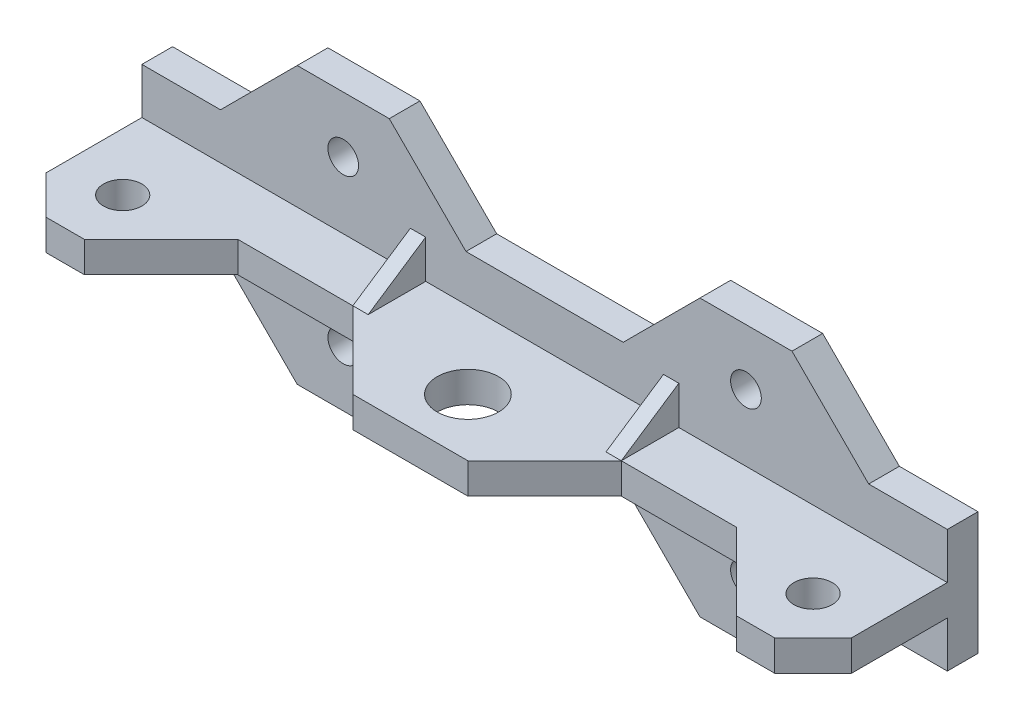
SolidWorks part; units mm, degrees
ref_plane "Front Plane" through (0, 0, 0) normal (0, 0, 1) x (1, 0, 0)
ref_plane "Top Plane" through (0, 0, 0) normal (0, 1, 0) x (1, 0, 0)
ref_plane "Right Plane" through (0, 0, 0) normal (1, 0, 0) x (0, 0, -1)
sketch "Sketch2" plane through (0, 0, 0) normal (0, 1, 0) x (1, 0, 0)
  line L2 (-52.5, 10) -> (52.5, 10)
  line L27 (-45, 0) -> (45, 0) construction
  line L34 (-50.1202, 2.5) -> (-6.1027, 2.5) construction
  line L36 (0, 10) -> (0, -7.5) construction
  line L37 (7.5, -7.5) -> (-7.5, -7.5)
  line L40 (-32.5, 2.5) -> (-17.5, 2.5)
  line L41 (-17.5, 2.5) -> (-7.5, -7.5)
  line L42 (50.1202, 2.5) -> (6.1027, 2.5) construction
  line L48 (-52.5, 10) -> (-52.5, 0)
  line L50 (-52.5, -2.5) -> (-47.5, -7.5)
  line L52 (-52.5, 0) -> (-52.5, -2.5)
  line L53 (-47.5, -7.5) -> (-42.5, -7.5)
  line L55 (-42.5, -7.5) -> (-32.5, 2.5)
  line L56 (42.5, -7.5) -> (32.5, 2.5)
  line L57 (47.5, -7.5) -> (42.5, -7.5)
  line L58 (52.5, 0) -> (52.5, -2.5)
  line L59 (52.5, -2.5) -> (47.5, -7.5)
  line L60 (52.5, 10) -> (52.5, 0)
  line L61 (17.5, 2.5) -> (7.5, -7.5)
  line L62 (32.5, 2.5) -> (17.5, 2.5)
  circle A0 centre (0, 0) radius 4
  circle A1 centre (-45, 0) radius 2.5
  circle A3 centre (45, 0) radius 2.5
  point P8 (-52.5, -7.5)
  point P9 (-52.5, -7.5)
  point P11 (-31.7458, 2.5)
  point P18 (0, 0)
  point P23 (0, -10)
  point P34 (52.5, -7.5)
  dimension "D1" = 8
  dimension "D2" = 5
  dimension "D3" = 10
  dimension "D4" = 45
  dimension "D5" = 5
  dimension "D6" = 7.5
  dimension "D7" = 45
  dimension "D8" = 7.5
  dimension "D9" = 45
  dimension "D10" = 17.5
  dimension "D11" = 7.5
  dimension "D12" = 0
  dimension "D14" = 7.5
extrude "Boss-Extrude1" add sketch "Sketch2" along normal blind 2 and the other way blind 2
sketch "Sketch4" plane through (0, 0, -10) normal (0, 0, -1) x (-1, 0, 0)
  line L1 (52.5, -18) -> (-52.5, -18) construction
  line L3 (52.5, 18) -> (-52.5, 18) construction
  line L6 (52.5, -8) -> (42.25, -8)
  line L7 (42.25, -8) -> (32.25, -18)
  line L8 (20.25, -18) -> (10.25, -8)
  line L9 (10.25, -8) -> (-10.25, -8)
  line L10 (52.5, 0) -> (-52.5, 0) construction
  line L11 (0, -18) -> (0, 0) construction
  line L12 (32.25, -18) -> (20.25, -18)
  line L13 (0, -3.3494) -> (52.5, -3.3494) construction
  line L14 (26.25, -3.3494) -> (26.25, -18) construction
  line L15 (52.5, -8) -> (52.5, 8)
  line L16 (-20.25, -18) -> (-10.25, -8)
  line L17 (-32.25, -18) -> (-20.25, -18)
  line L18 (-42.25, -8) -> (-32.25, -18)
  line L19 (-52.5, -8) -> (-42.25, -8)
  line L20 (-52.5, -8) -> (-52.5, 8)
  line L21 (-52.5, 8) -> (-42.25, 8)
  line L22 (-42.25, 8) -> (-32.25, 18)
  line L23 (-32.25, 18) -> (-20.25, 18)
  line L24 (-20.25, 18) -> (-10.25, 8)
  line L25 (10.25, 8) -> (-10.25, 8)
  line L26 (20.25, 18) -> (10.25, 8)
  line L27 (32.25, 18) -> (20.25, 18)
  line L28 (42.25, 8) -> (32.25, 18)
  line L29 (52.5, 8) -> (42.25, 8)
  circle A0 centre (26.25, -10.6747) radius 2
  circle A1 centre (-26.25, -10.6747) radius 2
  circle A2 centre (-26.25, 10.6747) radius 2
  circle A3 centre (26.25, 10.6747) radius 2
  point P26 (0, -8)
  point P30 (-26.25, -18)
  dimension "D5" = 4
  dimension "D1" = 8
  dimension "D2" = 18
  dimension "D3" = 12
  dimension "D4" = 135
extrude "Boss-Extrude2" add sketch "Sketch4" along normal blind 4
ref_plane "Plane1" through (-17.5, 0, 0) normal (-1, 0, 0) x (0, 0, 1)
sketch "Sketch5" plane through (-17.5, 0, 0) normal (-1, 0, 0) x (0, 0, 1)
  line L3 (0, 0) -> (-3.5975, 0) construction
  line L4 (-10, 7) -> (-10, 2)
  line L5 (-2.5, 2) -> (-10, 7)
  line L7 (-10, 8) -> (-10, 2) construction
  line L8 (-2.5, 2) -> (-10, 2)
  line L9 (-2.5, -2) -> (-10, -7)
  line L10 (-10, -7) -> (-10, -2)
  line L11 (-2.5, -2) -> (-10, -2)
  dimension "D1" = 5
extrude "Boss-Extrude3" add sketch "Sketch5" against normal blind 2
mirror "Mirror1" about plane through (0, 0, 0) normal (1, 0, 0) of "Boss-Extrude3"
